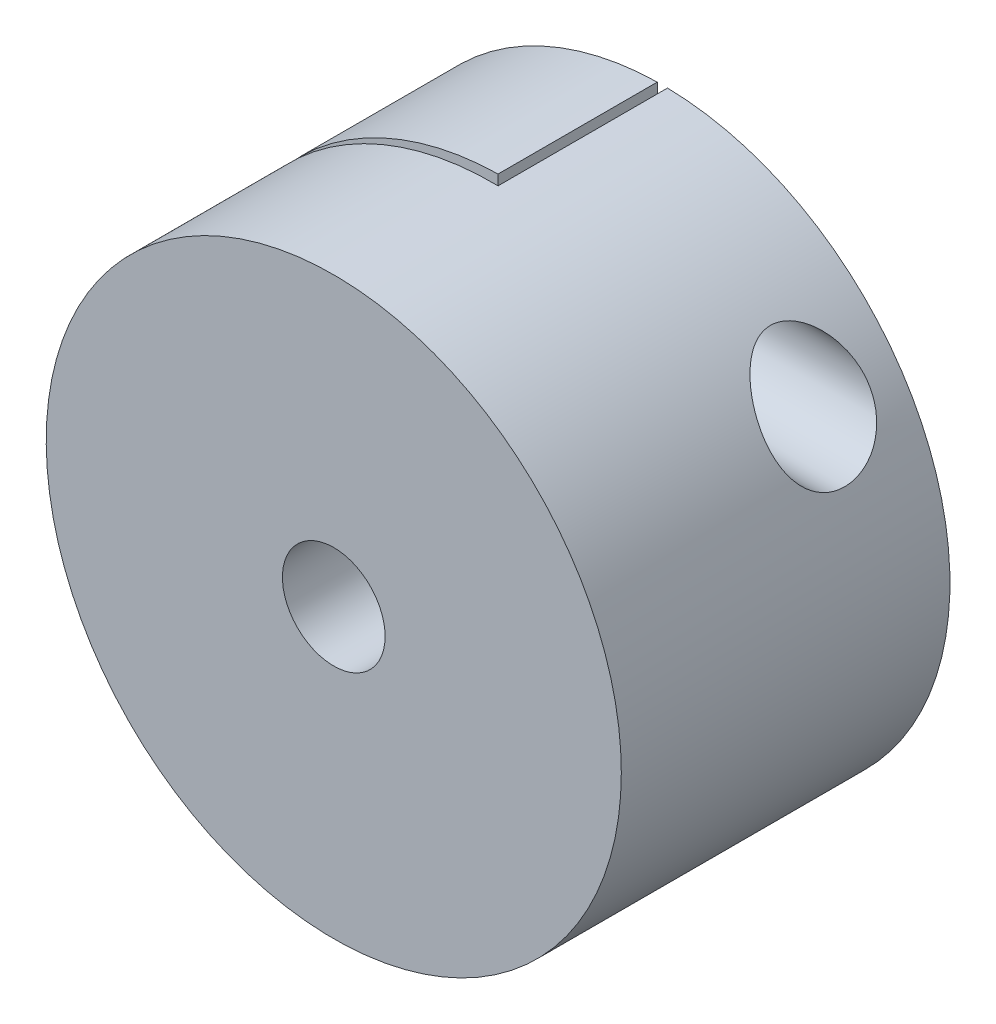
SolidWorks part; units mm, degrees
ref_plane "前视基准面" through (0, 0, 0) normal (0, 0, 1) x (1, 0, 0)
ref_plane "上视基准面" through (0, 0, 0) normal (0, 1, 0) x (1, 0, 0)
ref_plane "右视基准面" through (0, 0, 0) normal (1, 0, 0) x (0, 0, -1)
other "Configuration Table"
sketch "草图1" plane through (0, 0, 0) normal (0, 0, 1) x (1, 0, 0)
  circle A0 centre (0, 0) radius 14
  circle A1 centre (0, 0) radius 2.5
  dimension "D1" = 28
  dimension "D2" = 5
extrude "凸台-拉伸1" add sketch "草图1" along normal blind 16
sketch "草图2" plane through (0, 0, 0) normal (0, 1, 0) x (1, 0, 0)
  line L0 (-14, -7.75) -> (-14, -8.25)
  line L1 (-14, 0) -> (-14, -16) construction
  line L2 (-14, -8.25) -> (0.25, -8.25)
  line L4 (0.25, -8.25) -> (0.25, 0)
  line L5 (14, 0) -> (-14, 0) construction
  line L6 (0.25, 0) -> (-0.25, 0)
  line L7 (-0.25, 0) -> (-0.25, -7.75)
  line L8 (-0.25, -7.75) -> (-14, -7.75)
  point P5 (-14, -8)
  point P11 (0, 0)
  point P13 (-14, -6.9249)
  dimension "D1" = 8
  dimension "D2" = 0.5
  dimension "D3" = 0.5
extrude "切除-拉伸1" cut sketch "草图2" against normal through all both and the other way through all
sketch "草图3" plane through (0, 0, 0) normal (1, 0, 0) x (0, 0, -1)
  line L0 (0, -13.9978) -> (0, 13.9978) construction
  line L1 (0, 13.9978) -> (-8.25, 13.9978) construction
  circle A0 centre (-4, 7.9978) radius 2.5
  circle A1 centre (-4, 7.9978) radius 1.5
  dimension "D3" = 5
  dimension "D4" = 3
  dimension "D1" = 4
  dimension "D2" = 6
extrude "切除-拉伸2" cut sketch "草图3" against normal through all both and the other way through all contours A1
extrude "切除-拉伸3" cut sketch "草图3<4>" along normal through all from offset 3
sketch "草图3<4>" plane through (0, 0, 0) normal (1, 0, 0) x (0, 0, -1) same geometry as "草图3"
